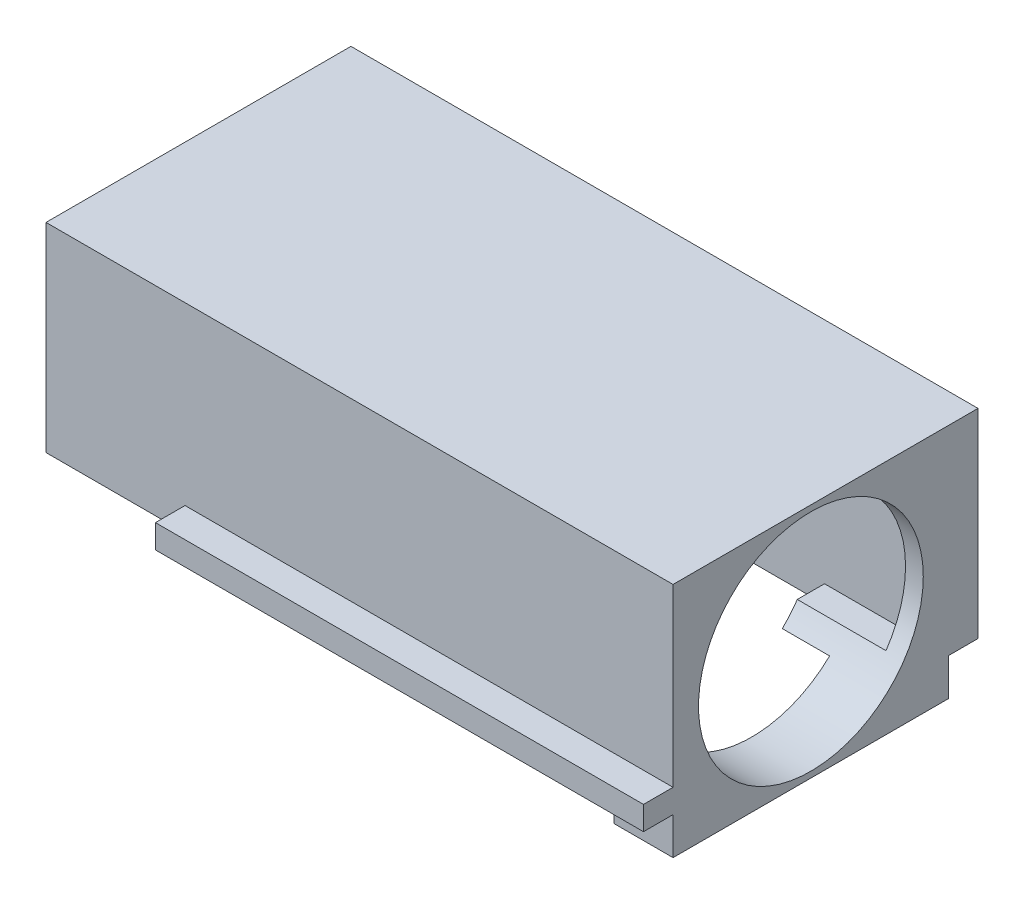
SolidWorks part; units mm, degrees
ref_plane "Front Plane" through (0, 0, 0) normal (0, 0, 1) x (1, 0, 0)
ref_plane "Top Plane" through (0, 0, 0) normal (0, 1, 0) x (1, 0, 0)
ref_plane "Right Plane" through (0, 0, 0) normal (1, 0, 0) x (0, 0, -1)
sketch "Sketch1" plane through (0, 0, 0) normal (0, 0, 1) x (1, 0, 0)
  line L0 (0, 0) -> (0, 40)
  line L1 (0, 40) -> (-106, 40)
  line L2 (-106, 40) -> (-106, 37)
  line L3 (-106, 37) -> (-3, 37)
  line L6 (0, 0) -> (-10, 0)
  line L7 (-10, 0) -> (-10, 6.3)
  line L8 (-10, 6.3) -> (-18, 6.3)
  line L9 (-18, 6.3) -> (-18, 9.3)
  line L10 (-3, 37) -> (-3, 9.3)
  line L11 (-3, 9.3) -> (-18, 9.3)
  dimension "D1" = 40
  dimension "D2" = 106
  dimension "D3" = 3
  dimension "D4" = 10
  dimension "D5" = 6.3
  dimension "D6" = 3
  dimension "D7" = 3
  dimension "D8" = 8
extrude "Boss-Extrude1" add sketch "Sketch1" along normal blind 46.6
sketch "Sketch2" plane through (0, 0, 0) normal (1, 0, 0) x (0, 0, -1)
  line L0 (0, 0) -> (0, 40) construction
  line L1 (-46.6, 0) -> (0, 0) construction
  circle A0 centre (-23.3, 20) radius 19
  dimension "D1" = 38
  dimension "D2" = 23.3
  dimension "D3" = 20
extrude "Cut-Extrude1" cut sketch "Sketch2" against normal up to next
sketch "Sketch3" plane through (-3, 0, 0) normal (-1, 0, 0) x (0, 0, 1)
  line L0 (46.6, 37) -> (31.7853, 37) construction
  line L1 (46.6, 6.3) -> (43.6, 6.3)
  line L2 (46.6, 6.3) -> (46.6, 37)
  line L3 (46.6, 37) -> (43.6, 37)
  line L4 (43.6, 6.3) -> (43.6, 37)
  dimension "D1" = 3
extrude "Boss-Extrude2" add sketch "Sketch3" along normal blind 103
sketch "Sketch4" plane through (0, 0, 0) normal (1, 0, 0) x (0, 0, -1)
  line L0 (-46.6, 0) -> (-46.6, 40) construction
  line L1 (-46.6, 6.3) -> (-51.6, 6.3)
  line L2 (-46.6, 6.3) -> (-46.6, 10.3)
  line L3 (-46.6, 10.3) -> (-51.6, 10.3)
  line L4 (-51.6, 6.3) -> (-51.6, 10.3)
  dimension "D1" = 0
  dimension "D2" = 4
  dimension "D3" = 5
extrude "Boss-Extrude3" add sketch "Sketch4" against normal blind 82.5
sketch "Sketch6" plane through (0, 0, 0) normal (1, 0, 0) x (0, 0, -1)
  line L1 (0, 40) -> (-3, 40)
  line L2 (0, 40) -> (0, 6.3)
  line L3 (0, 6.3) -> (-3, 6.3)
  line L4 (-3, 40) -> (-3, 6.3)
  dimension "D1" = 0
  dimension "D2" = 3
extrude "Boss-Extrude4" add sketch "Sketch6" against normal blind 106
sketch "Sketch8" plane through (0, 0, 0) normal (1, 0, 0) x (0, 0, -1)
  line L5 (0, 40) -> (4.95, 40)
  line L6 (0, 40) -> (0, 6.3)
  line L7 (0, 6.3) -> (4.95, 6.3)
  line L8 (4.95, 40) -> (4.95, 6.3)
  dimension "D1" = 4.95
  dimension "D2" = 6.3
extrude "Boss-Extrude5" add sketch "Sketch8" against normal blind 106
